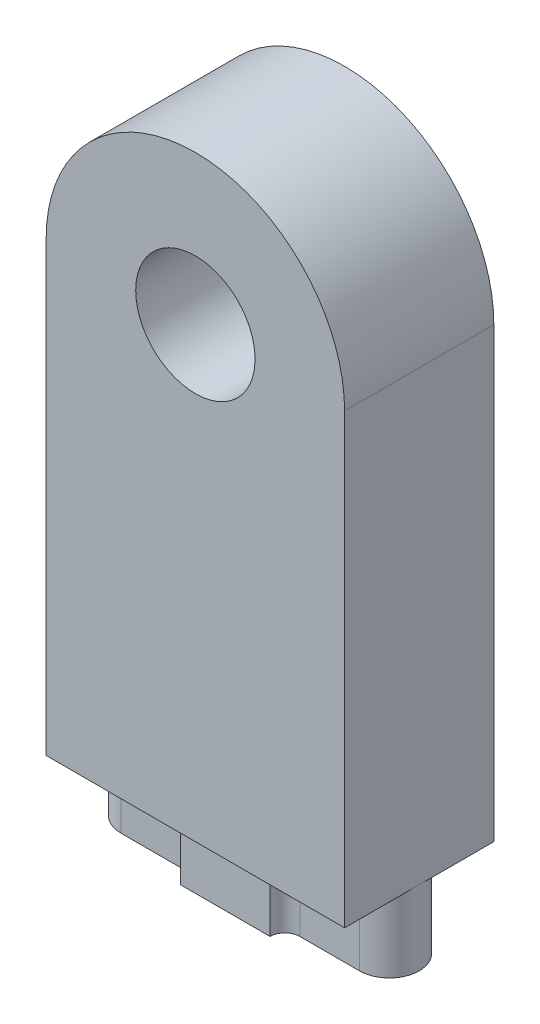
SolidWorks part; units mm, degrees
ref_plane "Front Plane" through (0, 0, 0) normal (0, 0, 1) x (1, 0, 0)
ref_plane "Top Plane" through (0, 0, 0) normal (0, 1, 0) x (1, 0, 0)
ref_plane "Right Plane" through (0, 0, 0) normal (1, 0, 0) x (0, 0, -1)
sketch "Sketch1" plane through (0, 0, 0) normal (0, 0, 1) x (1, 0, 0)
  line L0 (0, -44.7868) -> (0, 44.7868) construction
  line L1 (-10, -20) -> (10, -20)
  line L2 (-10, -20) -> (-10, 10)
  line L4 (10, -20) -> (10, 10)
  arc A0 (-10, 10) -> (10, 10) centre (0, 10) cw
  dimension "D1" = 20
  dimension "D2" = 30
extrude "Boss-Extrude1" add sketch "Sketch1" along normal blind 10
sketch "Sketch2" plane through (0, 0, 0) normal (0, 0, -1) x (-1, 0, 0)
  circle A0 centre (0, 10) radius 4
extrude "Cut-Extrude1" cut sketch "Sketch2" against normal blind 10
sketch "Sketch3" plane through (0, -20, 0) normal (0, -1, 0) x (1, 0, 0)
  line L0 (-8, 5) -> (8, 5) construction
  line L1 (0, -44.7868) -> (0, 44.7868) construction
  line L2 (-8, 7) -> (8, 7)
  line L3 (-8, 3) -> (8, 3)
  line L4 (44.2539, 0) -> (-44.2539, 0) construction
  arc A0 (-8, 7) -> (-8, 3) centre (-8, 5) ccw
  arc A1 (8, 3) -> (8, 7) centre (8, 5) ccw
  point P4 (0, 5)
  dimension "D1" = 2
  dimension "D2" = 16
  dimension "D3" = 5
extrude "Boss-Extrude2" add sketch "Sketch3" along normal blind 5
sketch "Sketch4" plane through (0, -20, 0) normal (0, -1, 0) x (1, 0, 0)
  line L0 (0, -44.7868) -> (0, 44.7868) construction
  line L1 (-1.75, 8) -> (1.75, 8)
  line L2 (-3, 6.75) -> (-3, 3.25)
  line L3 (-1.75, 2) -> (1.75, 2)
  line L4 (3, 6.75) -> (3, 3.25)
  line L5 (-3, 8) -> (3, 2) construction
  line L6 (-3, 2) -> (3, 8) construction
  line L7 (44.2539, 0) -> (-44.2539, 0) construction
  line L9 (-1.75, 2) -> (-3, 2)
  line L10 (-3, 2) -> (-3, 3.25)
  line L11 (3, 2) -> (3, 3.25)
  line L12 (1.75, 2) -> (3, 2)
  line L13 (3, 6.75) -> (3, 8)
  line L14 (3, 8) -> (1.75, 8)
  line L15 (-1.75, 8) -> (-3, 8)
  line L16 (-3, 8) -> (-3, 6.75)
  point P0 (0, 5)
  dimension "D1" = 6
  dimension "D2" = 6
  dimension "D3" = 5
extrude "Boss-Extrude3" add sketch "Sketch4" along normal blind 5
fillet "Fillet1" radius 1 4 edges at (3, -22.5, 7) (3, -22.5, 3) (-3, -22.5, 3) (-3, -22.5, 7)
